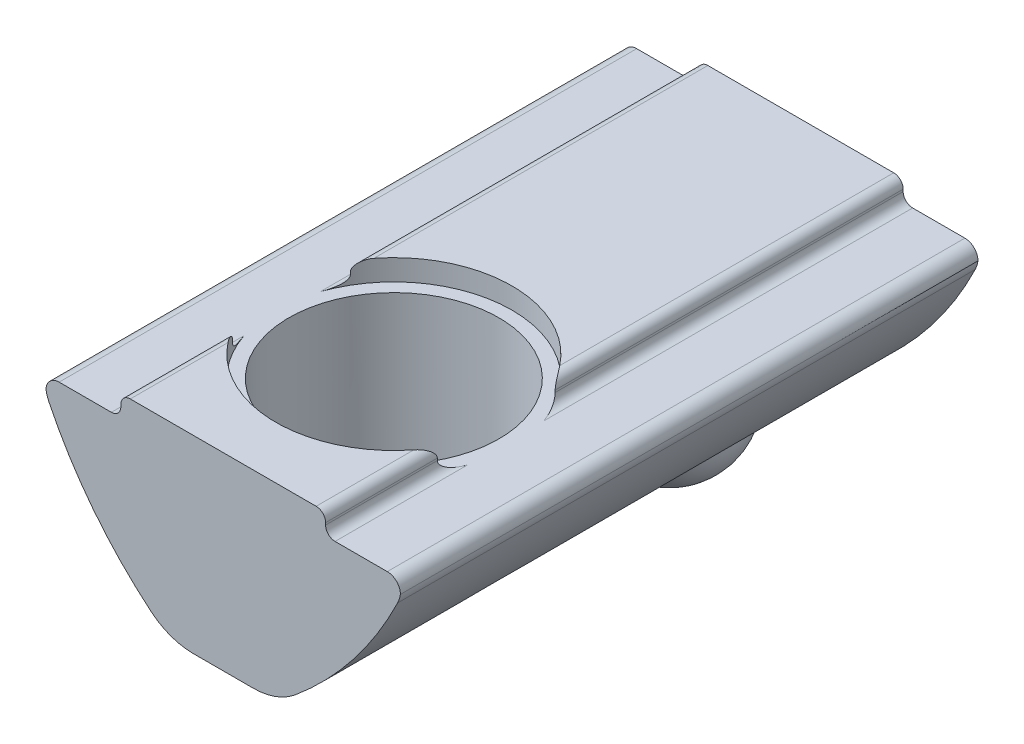
SolidWorks part; units mm, degrees
material "Plain Carbon Steel"
ref_plane "Front Plane" through (0, 0, 0) normal (0, 0, 1) x (1, 0, 0)
ref_plane "Top Plane" through (0, 0, 0) normal (0, 1, 0) x (1, 0, 0)
ref_plane "Right Plane" through (0, 0, 0) normal (1, 0, 0) x (0, 0, -1)
sketch "Sketch1" plane through (0, 0, 0) normal (0, 1, 0) x (1, 0, 0)
  circle A0 centre (0, 0) radius 4
  point P2 (4, 0)
  point P3 (-4, 0)
  dimension "D1" = 8
extrude "Boss-Extrude1" add sketch "Sketch1" against normal blind 16
sketch "Sketch2" plane through (0, -16, 0) normal (0, -1, 0) x (1, 0, 0)
  circle A1 centre (0, 0) radius 4
  circle A2 centre (0, 0) radius 4
  point P0 (0, -4)
  dimension "D1" = 0
curve "Helix/Spiral1" pitch 1.25 height 17.25 turns 13.8
sketch "Sketch3" plane through (0, 0, 0) normal (1, 0, 0) x (0, 0, -1)
  line L0 (4.1353, -15.9219) -> (3.0528, -16.5469) construction
  line L1 (3.0528, -16.5469) -> (4.1353, -17.1719) construction
  line L2 (4.1353, -17.1719) -> (4.1353, -15.9219) construction
  line L3 (3.1881, -16.4687) -> (3.1881, -16.625) construction
  line L4 (4, -16) -> (4, -17.0937) construction
  line L5 (3.0528, -16.5469) -> (3.1881, -16.5469) construction
  line L6 (4, -16.5469) -> (4.1353, -16.5469) construction
  line L8 (3.0528, -16.5469) -> (-4, -16.5469) construction
  line L9 (3.1881, -16.4687) -> (4.0677, -15.9609)
  line L10 (3.1881, -16.4687) -> (3.1881, -16.625)
  line L11 (3.1881, -16.625) -> (4.0677, -17.1328)
  line L12 (4.0677, -17.1328) -> (4.0677, -15.9609)
  line L14 (-4, -16.5469) -> (-4, -15.2969) construction
  line L15 (-4, -15.2969) -> (-4, -14.0469) construction
  line L16 (-4, -14.0469) -> (-4, -12.7969) construction
  line L17 (-4, -12.7969) -> (-4, -11.5469) construction
  line L18 (-4, 0) -> (-4, -16) construction
  point P15 (4.0677, -16.5469)
  dimension "D1" = 1.25
  dimension "D2" = 0.1562
sweep "Cut-Sweep1" cut profiles "Sketch3" path "Helix/Spiral1" align with end faces yes
sketch "SketchZ" plane through (0, 0, 0) normal (0, 0, 1) x (1, 0, 0)
  line L0 (0, -16.5469) -> (0, -15.9219) construction
  line L1 (0, -16.2344) -> (4, -16.2344) construction
  line L2 (4, -16.2344) -> (4, -14.9844) construction
  line L3 (0, -16.5469) -> (0, -15.2969) construction
sketch "Sketch4" plane through (0, -16, 0) normal (0, -1, 0) x (1, 0, 0)
  circle A0 centre (0, 0) radius 3.0528
extrude "Cut-Extrude1" cut sketch "Sketch4" against normal blind 1.25 draft 45 flip side to cut
sketch "Sketch5" plane through (0, 0, 0) normal (0, 0, 1) x (1, 0, 0)
  line L0 (0, 4.4) -> (0, 0)
  line L1 (0, 0) -> (-8.9, 0) construction
  line L2 (0, 4.4) -> (-4, 4.4)
  line L3 (-8.9, 0) -> (-8.9, 1.1) construction
  line L4 (-8.9, 1.1) -> (-7, 1.1) construction
  line L5 (0, 0) -> (0, -13.9857) construction
  line L6 (-7, 1.1) -> (-7, 0)
  line L7 (-7, 0) -> (0, 0)
  arc A0 (-7, 1.1) -> (-4, 4.4) centre (0, -2.25) cw
  dimension "D1" = 14
  dimension "D2" = 8.9
  dimension "D3" = 4.4
  dimension "D4" = 1.1
revolve "Revolve1" add sketch "Sketch5" angle 360 mid plane about L5
sketch "Sketch6" plane through (0, 4.4, 0) normal (0, 1, 0) x (1, 0, 0)
  line L1 (0, 2.8868) -> (-2.5, 1.4434)
  line L2 (-2.5, 1.4434) -> (-2.5, -1.4434)
  line L3 (-2.5, -1.4434) -> (0, -2.8868)
  line L4 (0, -2.8868) -> (2.5, -1.4434)
  line L5 (2.5, -1.4434) -> (2.5, 1.4434)
  line L6 (2.5, 1.4434) -> (0, 2.8868)
  circle A0 centre (0, 0) radius 2.5 construction
  dimension "D1" = 5
extrude "Cut-Extrude2" cut sketch "Sketch6" against normal blind 3
sketch "Sketch7" plane through (0, 4.4, 0) normal (0, 1, 0) x (1, 0, 0)
  circle A0 centre (0, 0) radius 2.8868
extrude "Cut-Extrude3" cut sketch "Sketch7" against normal blind 3 draft 45
sketch "Sketch8" plane through (0, 0, 0) normal (0, 0, 1) x (1, 0, 0)
  line L0 (6.75, -8) -> (6.75, -15.2) construction
  line L4 (6.75, -15.2) -> (-6.75, -15.2) construction
  line L7 (-6.75, -8) -> (6.75, -8) construction
  line L10 (0, 0) -> (0, -8) construction
  line L11 (-6.75, -15.2) -> (-6.75, -8) construction
  line L12 (-1.1419, -15.2) -> (1.1419, -15.2)
  line L13 (-3.54, -8) -> (3.54, -8)
  line L14 (-3.9, -8.36) -> (-3.9, -8.44)
  line L15 (-4.26, -8.8) -> (-6.25, -8.8)
  line L16 (3.9, -8.36) -> (3.9, -8.44)
  line L17 (4.26, -8.8) -> (6.25, -8.8)
  line L18 (0, -8) -> (0, -15.2) construction
  arc A1 (-2.741, -14.6217) -> (-6.6417, -9.6394) centre (6.8537, -3.0916) cw
  arc A2 (-3.54, -8) -> (-3.9, -8.36) centre (-3.54, -8.36) ccw
  arc A3 (-3.9, -8.44) -> (-4.26, -8.8) centre (-4.26, -8.44) cw
  arc A4 (-6.25, -8.8) -> (-6.75, -9.3) centre (-6.25, -9.3) ccw
  arc A5 (-6.75, -9.3) -> (-6.6417, -9.6394) centre (-5.5171, -9.0938) ccw
  arc A6 (-1.1419, -15.2) -> (-2.741, -14.6217) centre (-1.1419, -12.7) cw
  arc A7 (3.54, -8) -> (3.9, -8.36) centre (3.54, -8.36) cw
  arc A8 (3.9, -8.44) -> (4.26, -8.8) centre (4.26, -8.44) ccw
  arc A9 (6.25, -8.8) -> (6.75, -9.3) centre (6.25, -9.3) cw
  arc A10 (6.75, -9.3) -> (6.6417, -9.6394) centre (5.5171, -9.0938) cw
  arc A11 (2.741, -14.6217) -> (6.6417, -9.6394) centre (-6.8537, -3.0916) ccw
  arc A12 (1.1419, -15.2) -> (2.741, -14.6217) centre (1.1419, -12.7) ccw
  point P4 (-2, -15.2)
  point P25 (-2, -15.2)
  dimension "D1" = 13.5
  dimension "D3" = 4
  dimension "D4" = 15
  dimension "D6" = 7.8
  dimension "D8" = 0.36
  dimension "D9" = 1.25
  dimension "D10" = 0.5
  dimension "D11" = 2.5
  dimension "D2" = 8
  dimension "D5" = 7.2
  dimension "D7" = 0.8
extrude "Boss-Extrude2" add sketch "Sketch8" against normal blind 22 from offset 6.5 separate body
sketch "Sketch9" plane through (0, 0, 0) normal (0, 1, 0) x (1, 0, 0)
  line L0 (0, -6.5) -> (0, 0) construction
  line L1 (0, 0) -> (0, 10.5) construction
  line L3 (3.54, -6.5) -> (-3.54, -6.5) construction
  circle A1 centre (0, 10.5) radius 2.5 construction
  circle A2 centre (0, 0) radius 4
  circle A3 centre (0, 0) radius 4
  point P9 (0, 13)
  dimension "D3" = 5
  dimension "D1" = 17
  dimension "D2" = 0
extrude "Cut-Extrude4" cut sketch "Sketch9" against normal through all
sketch "Sketch10" plane through (0, 0, 0) normal (1, 0, 0) x (0, 0, -1)
  line L1 (10.5, -9.2) -> (13, -9.2)
  line L2 (10.5, -9.2) -> (10.5, -15.2)
  line L3 (10.5, -15.2) -> (13, -15.2)
  line L4 (13, -9.2) -> (13, -15.2)
  line L5 (15.5, -15.2) -> (3.8335, -15.2) construction
  line L8 (10.5, -9.2) -> (10.5, 0) construction
  dimension "D1" = 6
revolve "Cut-Revolve1" cut sketch "Sketch10" angle 360 about L8
sketch "Sketch11" plane through (0, 0, 0) normal (1, 0, 0) x (0, 0, -1)
  line L0 (10.5, -9.2) -> (10.5, -15.2) construction
  line L1 (13, -9.2) -> (13, -15.2) construction
  line L2 (10.5, -12.1) -> (10.5, -17.1)
  line L4 (15.5, -8) -> (1.8624, -8) construction
  arc A0 (10.5, -17.1) -> (10.5, -12.1) centre (10.5, -14.6) ccw
  dimension "D1" = 9.1
revolve "Revolve2" add sketch "Sketch11" angle 360 about L2
sketch "Sketch12" plane through (0, -8, 0) normal (0, 1, 0) x (1, 0, 0)
  circle A2 centre (0, 0) radius 4.5
  circle A3 centre (0, 0) radius 4.5
  dimension "D1" = 0.5
extrude "Cut-Extrude5" cut sketch "Sketch12" against normal up to surface (0.8 mm away) up to face at (5.255, -8.8, -4.5)
delete or keep bodies "Body-Delete/Keep 1" type delete bodies bodies 110
equation "\"D3@Helix/Spiral1\" = \"D4@Helix/Spiral1\" + \"D1@Boss-Extrude1\""
equation "\"D1@Sketch3\" = \"D4@Helix/Spiral1\""
equation "\"D2@Sketch3\" = \"D1@Sketch3\" / 8"
equation "\"D1@Cut-Extrude1\" = \"D4@Helix/Spiral1\""
equation "\"D1@Cut-Extrude2\" = \"D1@Sketch6\" * 3/5"
equation "\"D1@Cut-Extrude3\" = \"D1@Cut-Extrude2\""
equation "\"D4@Sketch5\" = \"D3@Sketch5\" * 1/4"
